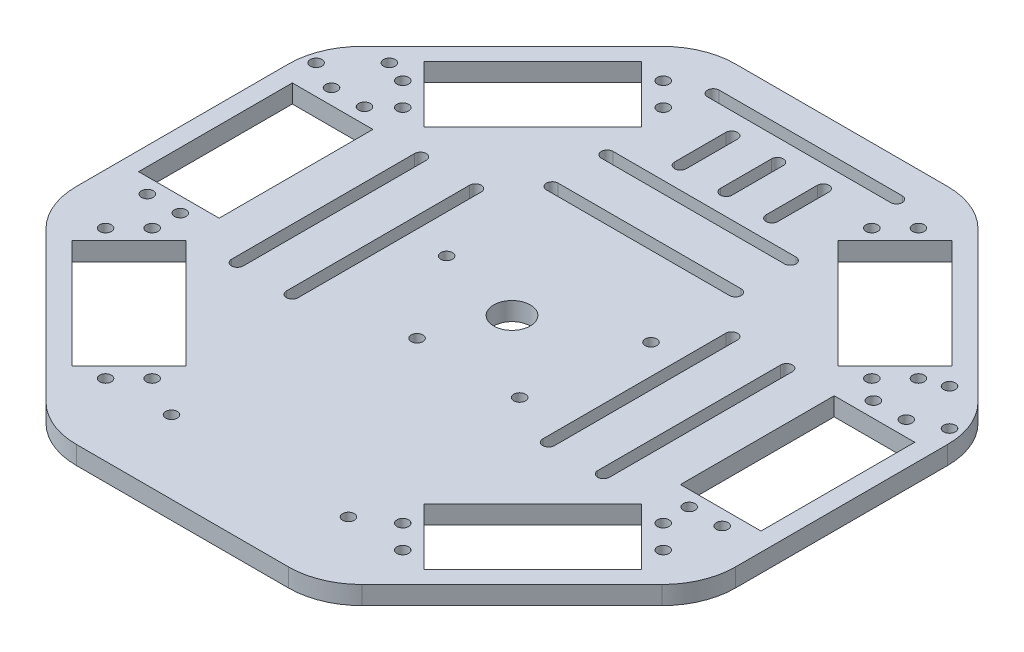
SolidWorks part; units mm, degrees
ref_plane "Front Plane" through (0, 0, 0) normal (0, 0, 1) x (1, 0, 0)
ref_plane "Top Plane" through (0, 0, 0) normal (0, 1, 0) x (1, 0, 0)
ref_plane "Right Plane" through (0, 0, 0) normal (1, 0, 0) x (0, 0, -1)
sketch "Sketch1" plane through (0, 0, 0) normal (0, 1, 0) x (1, 0, 0)
  line L1 (-90, -37.2792) -> (-37.2792, -90)
  line L2 (-37.2792, -90) -> (37.2792, -90)
  line L3 (37.2792, -90) -> (90, -37.2792)
  line L4 (90, -37.2792) -> (90, 37.2792)
  line L5 (90, 37.2792) -> (37.2792, 90)
  line L6 (37.2792, 90) -> (-37.2792, 90)
  line L7 (-37.2792, 90) -> (-90, 37.2792)
  line L8 (-90, 37.2792) -> (-90, -37.2792)
  line L12 (63.6396, -63.6396) -> (0, 0) construction
  line L21 (-20.4, -34.5422) -> (-34.5422, -20.4)
  line L22 (-20.4, -34.5422) -> (-50.0985, -64.2407)
  line L23 (-50.0985, -64.2407) -> (-64.2407, -50.0985)
  line L24 (-34.5422, -20.4) -> (-64.2407, -50.0985)
  line L25 (-38.85, -10) -> (-38.85, 10)
  line L26 (-38.85, -10) -> (-80.85, -10)
  line L27 (-80.85, -10) -> (-80.85, 10)
  line L28 (-38.85, 10) -> (-80.85, 10)
  line L29 (-34.5422, 20.4) -> (-20.4, 34.5422)
  line L30 (-34.5422, 20.4) -> (-64.2407, 50.0985)
  line L31 (-64.2407, 50.0985) -> (-50.0985, 64.2407)
  line L32 (-20.4, 34.5422) -> (-50.0985, 64.2407)
  line L37 (20.4, 34.5422) -> (34.5422, 20.4)
  line L38 (20.4, 34.5422) -> (50.0985, 64.2407)
  line L39 (50.0985, 64.2407) -> (64.2407, 50.0985)
  line L40 (34.5422, 20.4) -> (64.2407, 50.0985)
  line L41 (38.85, 10) -> (38.85, -10)
  line L42 (38.85, 10) -> (80.85, 10)
  line L43 (80.85, 10) -> (80.85, -10)
  line L44 (38.85, -10) -> (80.85, -10)
  circle A0 centre (0, 0) radius 90 construction
  circle A13 centre (0, 0) radius 90 construction
  circle A14 centre (-27.7186, -21.3546) radius 2.5
  circle A15 centre (-21.3546, -27.7186) radius 2.5
  circle A16 centre (-56.9221, -63.2861) radius 2.5
  circle A17 centre (-63.2861, -56.9221) radius 2.5
  circle A18 centre (0, 0) radius 90 construction
  circle A19 centre (-34.7, 4.5) radius 2.5
  circle A20 centre (-34.7, -4.5) radius 2.5
  circle A21 centre (-85, -4.5) radius 2.5
  circle A22 centre (-85, 4.5) radius 2.5
  circle A23 centre (0, 0) radius 90 construction
  circle A24 centre (-21.3546, 27.7186) radius 2.5
  circle A25 centre (-27.7186, 21.3546) radius 2.5
  circle A26 centre (-63.2861, 56.9221) radius 2.5
  circle A27 centre (-56.9221, 63.2861) radius 2.5
  circle A28 centre (0, 0) radius 90 construction
  circle A33 centre (0, 0) radius 90 construction
  circle A34 centre (27.7186, 21.3546) radius 2.5
  circle A35 centre (21.3546, 27.7186) radius 2.5
  circle A36 centre (56.9221, 63.2861) radius 2.5
  circle A37 centre (63.2861, 56.9221) radius 2.5
  circle A38 centre (0, 0) radius 90 construction
  circle A39 centre (34.7, -4.5) radius 2.5
  circle A40 centre (34.7, 4.5) radius 2.5
  circle A41 centre (85, 4.5) radius 2.5
  circle A42 centre (85, -4.5) radius 2.5
  circle A43 centre (0, 0) radius 90 construction
  point P15 (63.6396, -63.6396)
  point P16 (60.1041, -60.1041)
  point P17 (57.1696, -57.1696)
  point P121 (0, 0)
  dimension "D1" = 90
  dimension "D12" = 8
extrude "Baseplate" add sketch "Sketch1" along normal blind 5 contours L7 L8 L1 L2 L3 L4 L5 L6 A42 A41 A40 A39 A37 A36 A35 A34 A27 A26 A25 A24 A22 A21 A20 A19 A17 A16 A15 A14 L44 L41 | L29 L32 L31 L30 | L37 L40 L39 L38 | L41 L44 L43 L42 | L25 L28 L27 L26 | A27 | A26 | A25 | A24 | A22 | A21 | A19 | A20 | A14 | A15 | A17 | A16 | A40 | A41 | A42 | A35 | A34 | A39 | A37 | A36 | L21 L24 L23 L22 region at (1.7472, 0, 1.7472) region at (-59.85, 0, 0) region at (-42.3203, 0, -42.3203) region at (42.3203, 0, -42.3203) region at (59.85, 0, 0) region at (-27.7186, 0, 21.3546) region at (-21.3546, 0, 27.7186) region at (-56.9221, 0, 63.2861) region at (-63.2861, 0, 56.9221) region at (-34.7, 0, -4.5) region at (-34.7, 0, 4.5) region at (-85, 0, 4.5) region at (-85, 0, -4.5) region at (-21.3546, 0, -27.7186) region at (-27.7186, 0, -21.3546) region at (-63.2861, 0, -56.9221) region at (-56.9221, 0, -63.2861) region at (34.7, 0, -4.5) region at (85, 0, -4.5) region at (85, 0, 4.5)
fillet "Fillet1" radius 20 8 edges at (-90, 2.5, -37.2792) (-37.2792, 2.5, -90) (37.2792, 2.5, -90) (90, 2.5, -37.2792) (90, 2.5, 37.2792) (37.2792, 2.5, 90) (-37.2792, 2.5, 90) (-90, 2.5, 37.2792)
sketch "Sketch2" plane through (0, 5, 0) normal (0, 1, 0) x (1, 0, 0)
  line L0 (90, -28.9949) -> (90, 28.9949) construction
  line L1 (63, 25.0051) -> (85, 25.0051)
  line L2 (63, 25.0051) -> (63, -16.9949)
  line L3 (63, -16.9949) -> (85, -16.9949)
  line L4 (85, 25.0051) -> (85, -16.9949)
  circle A0 centre (78.5, 29.2051) radius 1.6
  circle A1 centre (69.5, 29.2051) radius 1.6
  circle A2 centre (69.5, -21.0949) radius 1.6
  circle A3 centre (78.5, -21.0949) radius 1.6
  point P8 (74, 25.0051)
  dimension "D1" = 3.2
  dimension "D2" = 9
  dimension "D3" = 50.3
  dimension "D4" = 22
  dimension "D5" = 42
  dimension "D6" = 4.2
  dimension "D7" = 4.5
  dimension "D8" = 5
  dimension "D9" = 12
extrude "Servo hole" cut sketch "Sketch2" against normal through all contours A0 | L4 L1 L2 L3 | A2 | A3 | A1 region at (74, 5, -4.0051) region at (78.5, 5, -29.2051) region at (69.5, 5, 21.0949) region at (78.5, 5, 21.0949)
sketch "Sketch3" plane through (0, 5, 0) normal (0, 1, 0) x (1, 0, 0)
  circle A0 centre (0, 0) radius 5
  dimension "D1" = 10
extrude "Center hole" cut sketch "Sketch3" against normal through all
pattern_circular "Servo hole pattern" count 8 over 360 about axis through (0, 5, 0) along (0, 1, 0) skipping 2, 3, 4, 5, 6 of "Servo hole"
sketch "Sketch4" plane through (0, 5, 0) normal (0, 1, 0) x (1, 0, 0)
  line L0 (-28.9949, -90) -> (28.9949, -90) construction
  line L1 (-90, 28.9949) -> (-90, -28.9949) construction
  circle A0 centre (-23, 5.1332) radius 1.6
  circle A1 centre (-23, -70) radius 1.6
  circle A2 centre (25.3362, 12.6262) radius 1.6
  circle A3 centre (25.3362, -70) radius 1.6
  circle A4 centre (-7.5585, -18.3745) radius 1.6
  circle A5 centre (20.4577, -18.3745) radius 1.6
  dimension "D1" = 3.2
  dimension "D8" = 20
  dimension "D2" = 7.493
  dimension "D3" = 48.3362
  dimension "D4" = 31.0007
  dimension "D5" = 51.6255
  dimension "D6" = 4.8785
  dimension "D7" = 28.0162
  dimension "D9" = 67
extrude "Arduino Screw holes" cut sketch "Sketch4" against normal through all
ref_plane "Midplane" through (0, 0, 0) normal (1, 0, 0) x (0, 0, -1)
mirror "Mirror1" about plane through (0, 0, 0) normal (1, 0, 0) of "Servo hole pattern", "Servo hole"
sketch "Sketch5" plane through (0, 5, 0) normal (0, 1, 0) x (1, 0, 0)
  line L0 (-25, 36) -> (25, 36) construction
  line L1 (-25, 37.6) -> (25, 37.6)
  line L2 (-25, 34.4) -> (25, 34.4)
  line L3 (-25, 51) -> (25, 51) construction
  line L4 (-25, 52.6) -> (25, 52.6)
  line L5 (-25, 49.4) -> (25, 49.4)
  line L6 (-50, 25) -> (-50, -25) construction
  line L7 (-48.4, 25) -> (-48.4, -25)
  line L8 (-51.6, 25) -> (-51.6, -25)
  line L9 (-35, 25) -> (-35, -25) construction
  line L10 (-33.4, 25) -> (-33.4, -25)
  line L11 (-36.6, 25) -> (-36.6, -25)
  line L12 (35, 25) -> (35, -25) construction
  line L13 (36.6, 25) -> (36.6, -25)
  line L14 (33.4, 25) -> (33.4, -25)
  line L15 (50, 25) -> (50, -25) construction
  line L16 (51.6, 25) -> (51.6, -25)
  line L17 (48.4, 25) -> (48.4, -25)
  line L18 (-25, 80) -> (25, 80) construction
  line L19 (-25, 81.6) -> (25, 81.6)
  line L20 (-25, 78.4) -> (25, 78.4)
  line L21 (-12.5, 72.5) -> (-12.5, 58.5) construction
  line L22 (-10.9, 72.5) -> (-10.9, 58.5)
  line L23 (-14.1, 72.5) -> (-14.1, 58.5)
  line L24 (12.5, 72.5) -> (12.5, 58.5) construction
  line L25 (14.1, 72.5) -> (14.1, 58.5)
  line L26 (10.9, 72.5) -> (10.9, 58.5)
  line L27 (28.9949, 90) -> (-28.9949, 90) construction
  line L28 (0, 72.5) -> (0, 58.5) construction
  line L29 (1.6, 72.5) -> (1.6, 58.5)
  line L30 (-1.6, 72.5) -> (-1.6, 58.5)
  arc A0 (-25, 37.6) -> (-25, 34.4) centre (-25, 36) ccw
  arc A1 (25, 34.4) -> (25, 37.6) centre (25, 36) ccw
  arc A2 (-25, 52.6) -> (-25, 49.4) centre (-25, 51) ccw
  arc A3 (25, 49.4) -> (25, 52.6) centre (25, 51) ccw
  arc A4 (-48.4, 25) -> (-51.6, 25) centre (-50, 25) ccw
  arc A5 (-51.6, -25) -> (-48.4, -25) centre (-50, -25) ccw
  arc A6 (-33.4, 25) -> (-36.6, 25) centre (-35, 25) ccw
  arc A7 (-36.6, -25) -> (-33.4, -25) centre (-35, -25) ccw
  arc A8 (36.6, 25) -> (33.4, 25) centre (35, 25) ccw
  arc A9 (33.4, -25) -> (36.6, -25) centre (35, -25) ccw
  arc A10 (51.6, 25) -> (48.4, 25) centre (50, 25) ccw
  arc A11 (48.4, -25) -> (51.6, -25) centre (50, -25) ccw
  arc A12 (-25, 81.6) -> (-25, 78.4) centre (-25, 80) ccw
  arc A13 (25, 78.4) -> (25, 81.6) centre (25, 80) ccw
  arc A14 (-10.9, 72.5) -> (-14.1, 72.5) centre (-12.5, 72.5) ccw
  arc A15 (-14.1, 58.5) -> (-10.9, 58.5) centre (-12.5, 58.5) ccw
  arc A16 (14.1, 72.5) -> (10.9, 72.5) centre (12.5, 72.5) ccw
  arc A17 (10.9, 58.5) -> (14.1, 58.5) centre (12.5, 58.5) ccw
  arc A18 (1.6, 72.5) -> (-1.6, 72.5) centre (0, 72.5) ccw
  arc A19 (-1.6, 58.5) -> (1.6, 58.5) centre (0, 58.5) ccw
  point P2 (0, 36)
  point P7 (0, 51)
  point P14 (-50, 0)
  point P21 (-35, 0)
  point P28 (35, 0)
  point P35 (50, 0)
  point P42 (0, 80)
  point P48 (-12.5, 65.5)
  point P57 (12.5, 65.5)
  point P64 (0, 65.5)
  point P71 (0, 0)
  point P72 (0, 0)
  dimension "D1" = 1.6
  dimension "D7" = 50
  dimension "D2" = 15
  dimension "D3" = 15
  dimension "D4" = 15
  dimension "D5" = 10
  dimension "D6" = 50
  dimension "D8" = 35
  dimension "D9" = 35
  dimension "D10" = 36
  dimension "D11" = 12.5
  dimension "D12" = 12.5
  dimension "D13" = 7.5
  dimension "D14" = 7.5
extrude "Slits" cut sketch "Sketch5" against normal through all contours L30 A19 L29 A18 | L26 A17 L25 A16 | L5 A3 L4 A2 | L2 A1 L1 A0 | L8 A5 L7 A4 | L11 A7 L10 A6 | L14 A9 L13 A8 | L17 A11 L16 A10 | L19 A13 L20 A12 | L22 A15 L23 A14 region at (0, 5, -36) region at (0, 5, -51) region at (-50, 5, 0) region at (-35, 5, 0) region at (35, 5, 0) region at (50, 5, 0) region at (12.5, 5, -65.5) region at (0, 5, -65.5)
sketch "Sketch6" plane through (0, 5, 0) normal (0, 1, 0) x (1, 0, 0)
  circle A0 centre (-76.5, 43) radius 1.6
  circle A1 centre (-86.5, 33) radius 1.6
  point P4 (-86.0341, 33.1791)
  dimension "D1" = 3.2
  dimension "D2" = 10
  dimension "D3" = 10
  dimension "D4" = 86.5
  dimension "D5" = 43
extrude "Exterior Screw Holes" cut sketch "Sketch6" against normal through all
ref_plane "Plane1" through (0, 0, 0) normal (0, 0, 1) x (1, 0, 0)
mirror "Mirror2" about plane through (0, 0, 0) normal (1, 0, 0) of "Exterior Screw Holes"
